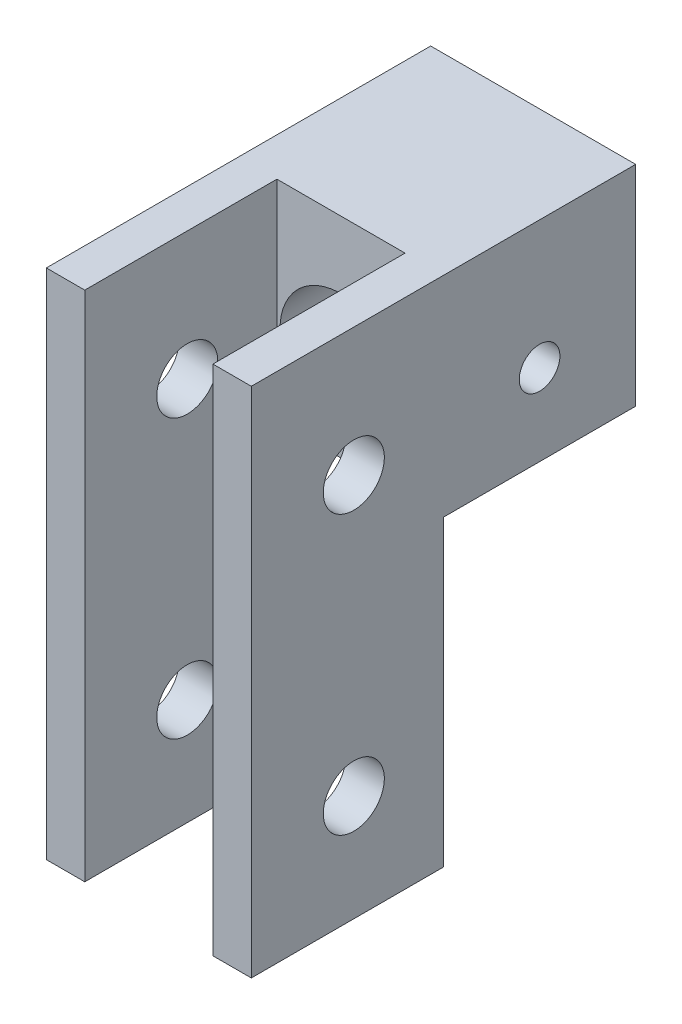
SolidWorks part; units mm, degrees
material "Delrin 2700 NC010, Low Viscosity Acetal Copolymer (SS)"
ref_plane "Front" through (0, 0, 0) normal (0, 0, 1) x (1, 0, 0)
ref_plane "Top" through (0, 0, 0) normal (0, 1, 0) x (1, 0, 0)
ref_plane "Right" through (0, 0, 0) normal (1, 0, 0) x (0, 0, -1)
sketch "Sketch1" plane through (0, 0, 0) normal (0, 0, 1) x (1, 0, 0)
  line L0 (0, 0) -> (0, 10) construction
  line L5 (8, -30) -> (8, 10)
  line L6 (8, 10) -> (-8, 10)
  line L7 (-8, 10) -> (-8, -30)
  line L8 (-8, -30) -> (8, -30)
  circle A3 centre (0, 0) radius 2.6 construction
  dimension "D2" = 16
  dimension "D4" = 5.2
  dimension "D6" = 10
  dimension "D7" = 40
extrude "Boss-Extrude1" add sketch "Sketch1" along normal blind 30
hole_wizard "3/8 (0.3750) Dowel Hole1" positions "Sketch2" profile "Sketch3" hole size "3/8" standard "ANSI Inch" end condition through all
sketch "Sketch2" plane through (0, 0, 30) normal (0, 0, 1) x (1, 0, 0)
  point P0 (0, 0)
sketch "Sketch3" plane through (0, 0, 30) normal (1, 0, 0) x (0, -1, 0)
  line L0 (0, 0) -> (0, 30)
  line L1 (0, 30) -> (4.7625, 30)
  line L2 (4.7625, 30) -> (4.7625, 0)
  line L5 (4.7625, 0) -> (0, 0)
  line L11 (0, -6.35) -> (0, 107.95) construction
  dimension "Thru Hole Dia." = 9.525
  dimension "Thru Hole Depth" = 30
hole_wizard "1/8 (0.1250) Dowel Hole1" positions "Sketch4" profile "Sketch5" hole size "1/8" standard "ANSI Inch" end condition through all
sketch "Sketch4" plane through (-8, 0, 0) normal (-1, 0, 0) x (0, 0, 1)
  line L0 (7.5, 10) -> (7.5, 0) construction
  line L2 (30, 10) -> (0, 10) construction
  point P0 (7.5, 0)
  point P14 (7.5, 30)
  dimension "D1" = 7.5
sketch "Sketch5" plane through (-8, 0, 7.5) normal (0, 1, 0) x (0, 0, 1)
  line L0 (0, 0) -> (0, 16)
  line L1 (0, 16) -> (1.5875, 16)
  line L2 (1.5875, 16) -> (1.5875, 0)
  line L5 (1.5875, 0) -> (0, 0)
  line L11 (0, -6.35) -> (0, 107.95) construction
  dimension "Thru Hole Dia." = 3.175
  dimension "Thru Hole Depth" = 16
sketch "Sketch7" plane through (0, 0, 30) normal (0, 0, 1) x (1, 0, 0)
  line L0 (8, 10) -> (-8, 10) construction
  line L1 (5, 10) -> (-5, 10)
  line L2 (5, 10) -> (5, -30)
  line L3 (5, -30) -> (-5, -30)
  line L4 (-5, 10) -> (-5, -30)
  line L5 (0, 0) -> (0, 10) construction
  line L6 (-8, -30) -> (8, -30) construction
  point P11 (0, 0)
  dimension "D1" = 10
extrude "Cut-Extrude1" cut sketch "Sketch7" against normal offset from surface (15 mm away) 15 up to face at (4.7625, 0, 0)
hole_wizard "3/16 (0.1875) Diameter Hole1" positions "Sketch8" profile "Sketch9" hole size "3/16" standard "ANSI Inch" end condition through all
sketch "Sketch8" plane through (-8, 0, 0) normal (-1, 0, 0) x (0, 0, 1)
  line L0 (22, -21.7) -> (22, 0) construction
  line L1 (22, 0) -> (15, 0) construction
  line L3 (15, 10) -> (15, -30) construction
  point P0 (22, 0)
  point P2 (22, -21.7)
  point P12 (0, 0)
  dimension "D1" = 7
  dimension "D2" = 21.7
sketch "Sketch9" plane through (-8, 0, 22) normal (0, 1, 0) x (0, 0, 1)
  line L0 (0, 0) -> (0, 16)
  line L1 (0, 16) -> (2.3812, 16)
  line L2 (2.3812, 16) -> (2.3812, 0)
  line L5 (2.3812, 0) -> (0, 0)
  line L11 (0, -6.35) -> (0, 107.95) construction
  dimension "Thru Hole Dia." = 4.7625
  dimension "Thru Hole Depth" = 16
sketch "Sketch10" plane through (0, 0, 0) normal (0, 0, -1) x (-1, 0, 0)
  line L0 (8, 10) -> (8, -30) construction
  line L1 (-8, -30) -> (8, -30)
  line L2 (-8, -30) -> (-8, -6.35)
  line L3 (-8, -6.35) -> (8, -6.35)
  line L4 (8, -30) -> (8, -6.35)
  dimension "D1" = 6.35
extrude "Cut-Extrude2" cut sketch "Sketch10" against normal up to surface (15 mm away) up to face at (0, -10, 15)
